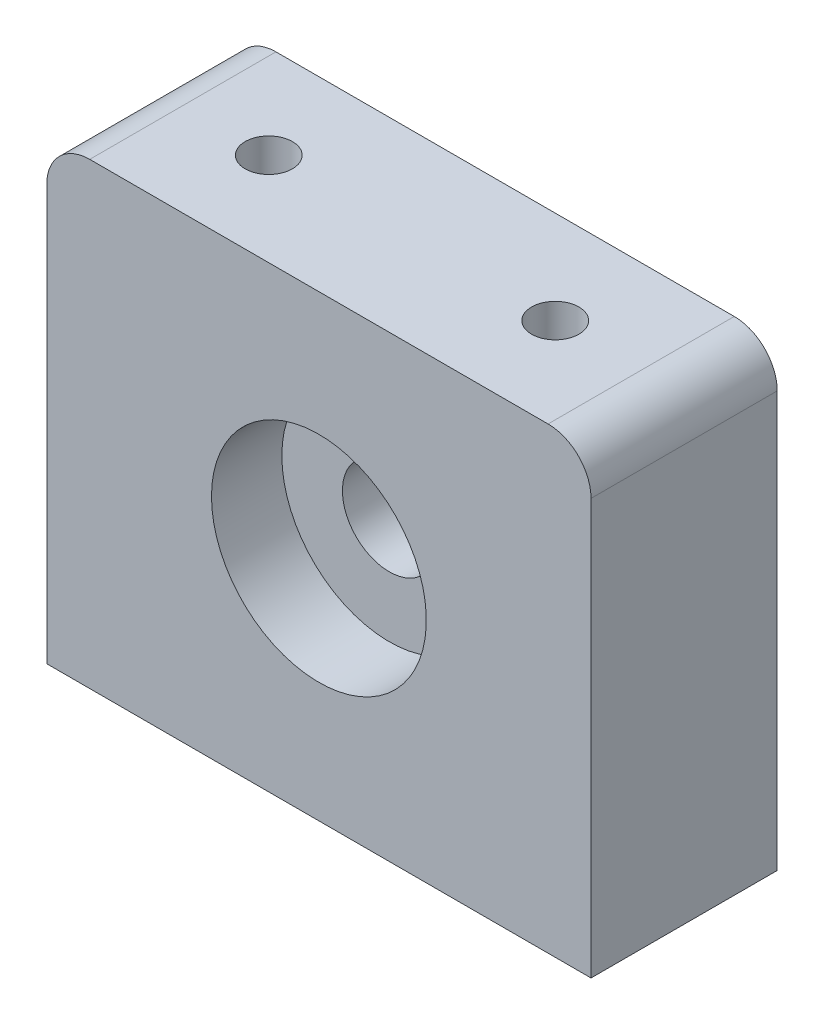
SolidWorks part; units mm, degrees
ref_plane "Front Plane" through (0, 0, 0) normal (0, 0, 1) x (1, 0, 0)
ref_plane "Top Plane" through (0, 0, 0) normal (0, 1, 0) x (1, 0, 0)
ref_plane "Right Plane" through (0, 0, 0) normal (1, 0, 0) x (0, 0, -1)
sketch "Sketch1" plane through (0, 0, 0) normal (0, 0, 1) x (1, 0, 0)
  line L0 (0, -26.1041) -> (0, 52.7781) construction
  line L1 (-16, 32) -> (16, 32)
  line L3 (0, 0) -> (-19, 0)
  line L4 (19, 0) -> (19, 29)
  line L7 (-19, 0) -> (-19, 29)
  line L8 (0, 0) -> (19, 0)
  circle A0 centre (0, 15.874) radius 7.5
  arc A1 (19, 29) -> (16, 32) centre (16, 29) ccw
  arc A2 (-19, 29) -> (-16, 32) centre (-16, 29) cw
  point P5 (19, 32)
  point P10 (-19, 32)
  point P11 (0, 4.699)
  point P12 (0, 28.448)
  point P15 (0, 8.374)
  dimension "D6" = 15
  dimension "D2" = 3
  dimension "D1" = 32
  dimension "D5" = 15.874
  dimension "D7" = 38
extrude "Boss-Extrude1" add sketch "Sketch1" along normal blind 13
ref_plane "Plane1" through (0, 0, 6.5) normal (0, 0, 1) x (1, 0, 0)
sketch "Sketch3" plane through (0, 0, 6.5) normal (0, 0, 1) x (1, 0, 0)
  circle A0 centre (0, 15.874) radius 3.2703
  circle A1 centre (0, 15.874) radius 8.7376
  dimension "D1" = 6.5405
  dimension "D2" = 17.4752
extrude "Boss-Extrude2" add sketch "Sketch3" along normal blind 1.5875 and the other way blind 1.5875
sketch "Sketch7" plane through (0, 0, 0) normal (0, -1, 0) x (1, 0, 0)
  line L0 (-19, 13) -> (19, 0) construction
  line L1 (0, 0) -> (0, 13) construction
  line L2 (-19, 13) -> (19, 13) construction
  point P9 (0, 6.5)
hole_wizard "M4x0.7 Tapped Hole1" positions "Sketch5" profile "Sketch6" tap size "M4x0.7" standard "ANSI Metric"
sketch "Sketch5" plane through (0, 0, 0) normal (0, -1, 0) x (-1, 0, 0)
  point P0 (10, -6.5)
  point P2 (-10, -6.5)
  dimension "D1" = 10
  dimension "D2" = 0
  dimension "D3" = 10
  dimension "D4" = 0
sketch "Sketch6" plane through (-10, 0, 6.5) normal (1, 0, 0) x (0, 0, -1)
  line L0 (0, 0) -> (0, 11.1006)
  line L1 (0, 11.1006) -> (1.65, 10.1092)
  line L2 (1.65, 10.1092) -> (1.65, 0)
  line L5 (1.65, 0) -> (0, 0)
  line L10 (0, 11.1006) -> (-1.65, 10.1092) construction
  line L11 (0, -6.35) -> (0, 107.95) construction
  dimension "Tap Drill Dia." = 3.3
  dimension "Tap Drill Depth" = 10.1092
  dimension "Drill Angle" = 118
cosmetic thread "Hole Thread1" parameters "D1"=8.001, "D2"=4
cosmetic thread "Hole Thread2" parameters "D1"=8.001, "D2"=4
hole_wizard "M4x0.7 Tapped Hole2" positions "Sketch8" profile "Sketch10" tap size "M4x0.7" standard "ANSI Metric"
sketch "Sketch8" plane through (0, 32, 0) normal (0, 1, 0) x (1, 0, 0)
  point P0 (-10, -6.5)
  point P3 (10, -6.5)
sketch "Sketch10" plane through (-10, 32, 6.5) normal (1, 0, 0) x (0, 0, 1)
  line L0 (0, 0) -> (0, 10.9914)
  line L1 (0, 10.9914) -> (1.65, 10)
  line L2 (1.65, 10) -> (1.65, 0)
  line L5 (1.65, 0) -> (0, 0)
  line L10 (0, 10.9914) -> (-1.65, 10) construction
  line L11 (0, -6.35) -> (0, 107.95) construction
  dimension "Tap Drill Dia." = 3.3
  dimension "Tap Drill Depth" = 10
  dimension "Drill Angle" = 118
cosmetic thread "Hole Thread3" parameters "D1"=8, "D2"=4
cosmetic thread "Hole Thread4" parameters "D1"=8, "D2"=4
equation "\"0.095inin\"=0.085"
